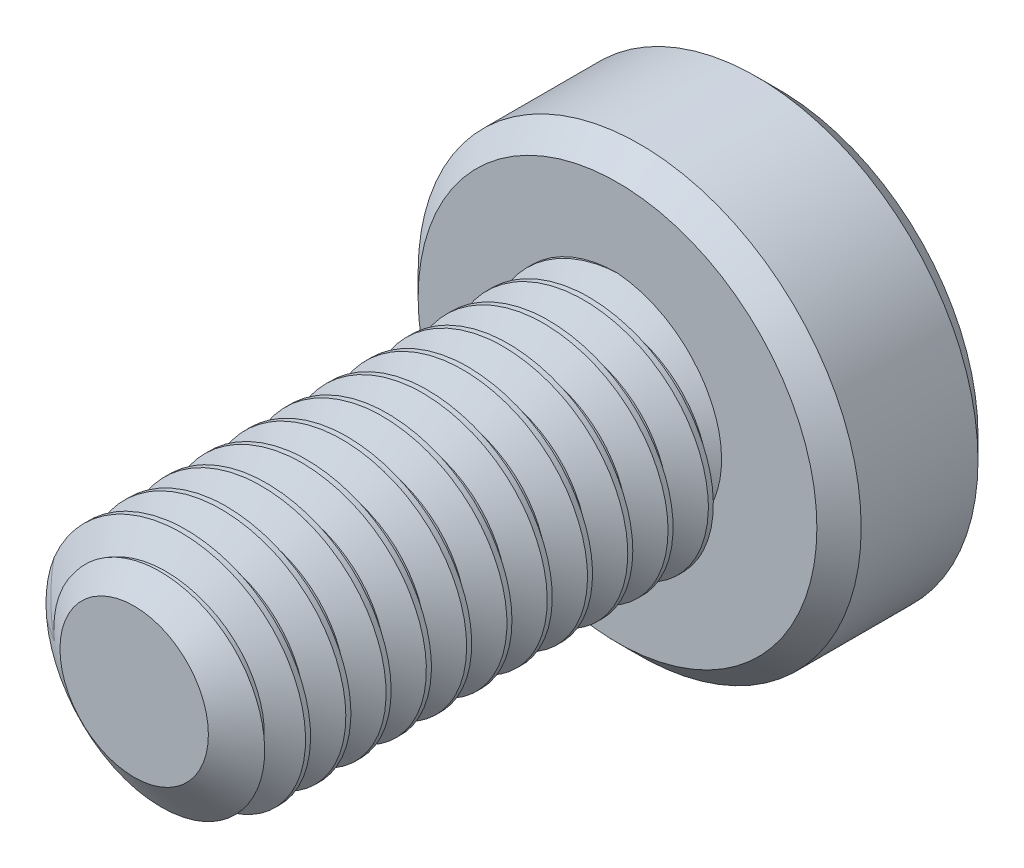
SolidWorks part; units mm, degrees
other "DetailItem1"
ref_plane "Front Plane" through (0, 0, 0) normal (0, 0, 1) x (1, 0, 0)
ref_plane "Top Plane" through (0, 0, 0) normal (0, 1, 0) x (1, 0, 0)
ref_plane "Right Plane" through (0, 0, 0) normal (1, 0, 0) x (0, 0, -1)
sketch "Sketch1" plane through (0, 0, 0) normal (0, 0, 1) x (1, 0, 0)
  circle A0 centre (0, 0) radius 1.5
  dimension "OD" = 3
extrude "Extrude1" add sketch "Sketch1" against normal blind 6
sketch "Sketch2" plane through (0, 0, 0) normal (0, 0, 1) x (1, 0, 0)
  circle A0 centre (0, 0) radius 1.5 construction
  circle A1 centre (0, 0) radius 1.5
curve "Helix/Spiral1" pitch 0.5 height 6.5 radius 1.5 centre (0, 0, 0) axis (0, 0, -1) start towards (0, 1, 0) parameters "pitch"=0.5
sketch "Sketch3" plane through (0, 0, 0) normal (1, 0, 0) x (0, 0, -1)
  line L0 (-0.4375, 1.5) -> (-0.25, 1.1752)
  line L1 (-0.25, 1.1752) -> (-0.1875, 1.1752)
  line L2 (-0.1875, 1.1752) -> (0, 1.5)
  line L3 (-0.4375, 1.5) -> (0, 1.5)
  line L4 (-0.2188, 1.5) -> (-0.2188, 1.1752) construction
  line L5 (-0.3438, 1.3376) -> (-0.0938, 1.3376) construction
  line L6 (0, 1.5) -> (0, -1.5) construction
  dimension "D1" = 0.0625
  dimension "D2" = 0.25
  dimension "D3" = 60
sweep "Cut-Sweep1" cut profiles "Sketch3" path "Helix/Spiral1"
sketch "Sketch4" plane through (0, 0, 0) normal (1, 0, 0) x (0, 0, -1)
  line L0 (0.4053, 1.5) -> (0, 0.9212)
  line L1 (0, 0.9212) -> (0, 1.5)
  line L2 (0.4053, 1.5) -> (0, 1.5)
  line L3 (-0.4375, 1.5) -> (0, 1.5) construction
  line L4 (0, 0) -> (7.0209, 0) construction
  dimension "D1" = 55
  dimension "D2" = 0.254
revolve "Cut-Revolve1" cut sketch "Sketch4" angle 360 about L4
sketch "Sketch6" plane through (0, 0, -6) normal (0, 0, -1) x (-1, 0, 0)
  circle A0 centre (0, 0) radius 2.75
  dimension "head dia" = 5.5
extrude "Extrude2" add sketch "Sketch6" along normal blind 2
sketch "Sketch7" plane through (0, 0, -8) normal (0, 0, -1) x (-1, 0, 0)
  line L1 (0, 1.1547) -> (-1, 0.5774)
  line L2 (-1, 0.5774) -> (-1, -0.5774)
  line L3 (-1, -0.5774) -> (0, -1.1547)
  line L4 (0, -1.1547) -> (1, -0.5774)
  line L5 (1, -0.5774) -> (1, 0.5774)
  line L6 (1, 0.5774) -> (0, 1.1547)
  circle A0 centre (0, 0) radius 1 construction
  dimension "hex dia" = 2
extrude "Cut-Extrude1" cut sketch "Sketch7" against normal blind 1.5
sketch "Sketch8" plane through (0, 0, -8) normal (0, 0, -1) x (-1, 0, 0)
  circle A0 centre (0, 0) radius 1.1547
extrude "Cut-Extrude2" cut sketch "Sketch8" against normal through all draft 45
chamfer "Chamfer1" distance 0.275 angle 45 2 edges at (-2.75, 0, -8) (-2.75, 0, -6)
sketch "Sketch10" plane through (0, 0, -6) normal (0, 0, 1) x (1, 0, 0)
  circle A1 centre (0, 0) radius 1.5
  circle A2 centre (0, 0) radius 1.5
  dimension "D1" = 0
ref_plane "Plane1" through (0, 0, -30) normal (0, 0, 1) x (1, 0, 0)
extrude "partial thread" [suppressed] add sketch "Sketch10" along normal up to surface (20 mm away) separate body up to plane "Plane1"
chamfer "Chamfer2" [suppressed] distance 0.06 angle 45
combine bodies "Combine1" [suppressed] operation type add bodies to combine 107 108
sketch "Sketch9" plane through (0, 0, 0) normal (1, 0, 0) x (0, 0, -1)
  line L0 (0, 1.5) -> (0, -1.5) construction
  line L1 (1.25, 1.5) -> (1.25, -1.5) construction
  dimension "D1" = 1.25
  dimension "D4" = 0.635
  dimension "D5" = 0.3302
equation "\"D3@Helix/Spiral1\" = \"screw length@Extrude1\"+\"pitch@Helix/Spiral1\""
equation "\"D1@Sketch3\" = \"pitch@Helix/Spiral1\"*.125"
equation "\"D2@Sketch3\" = \"pitch@Helix/Spiral1\"*.5"
equation "\"D1@Cut-Extrude1\" = \"hex dia@Sketch7\"*.75"
equation "\"D1@Chamfer1\" = \"head dia@Sketch6\"*.05"
equation "\"D1@Sketch9\" = \"pitch@Helix/Spiral1\"*2.5"
equation "\"D1@Chamfer2\"=\"OD@Sketch1\"*.02"
